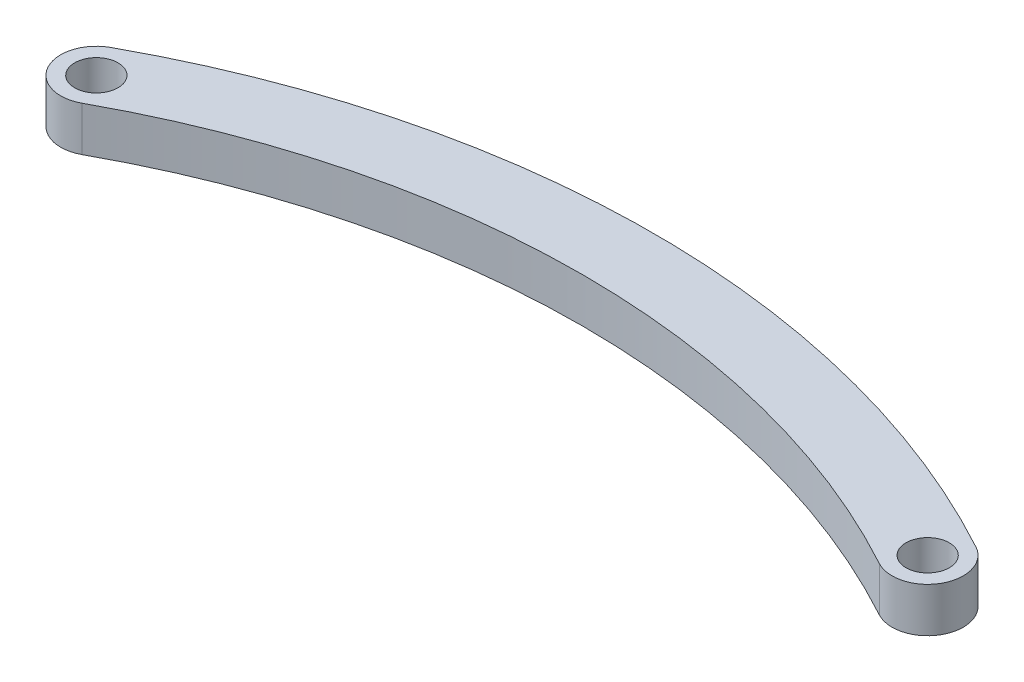
SolidWorks part; units mm, degrees
ref_plane "Front Plane" through (0, 0, 0) normal (0, 0, 1) x (1, 0, 0)
ref_plane "Top Plane" through (0, 0, 0) normal (0, 1, 0) x (1, 0, 0)
ref_plane "Right Plane" through (0, 0, 0) normal (1, 0, 0) x (0, 0, -1)
sketch "Esquisse1" plane through (0, 0, 0) normal (0, 1, 0) x (1, 0, 0)
  line L0 (-35, 0) -> (0, 0) construction
  line L1 (0, 0) -> (35, 0) construction
  circle A0 centre (-35, 0) radius 1.825
  circle A1 centre (35, 0) radius 1.825
  circle A2 centre (-35, 0) radius 3
  circle A3 centre (35, 0) radius 3
  circle A4 centre (0, -64.0625) radius 70
  circle A5 centre (0, -64.0625) radius 76
  dimension "D2" = 3.65
  dimension "D3" = 6
  dimension "D4" = 140
  dimension "D5" = 152
  dimension "D1" = 35
extrude "Boss.-Extru.1" add sketch "Esquisse1" along normal blind 3.75 contours A3 A5 A2 A4 | A2 A0 | A3 A1 region at (-32.4928, 0, 1.4872) region at (0, 0, -6.3427) region at (37.5072, 0, -1.4872)
